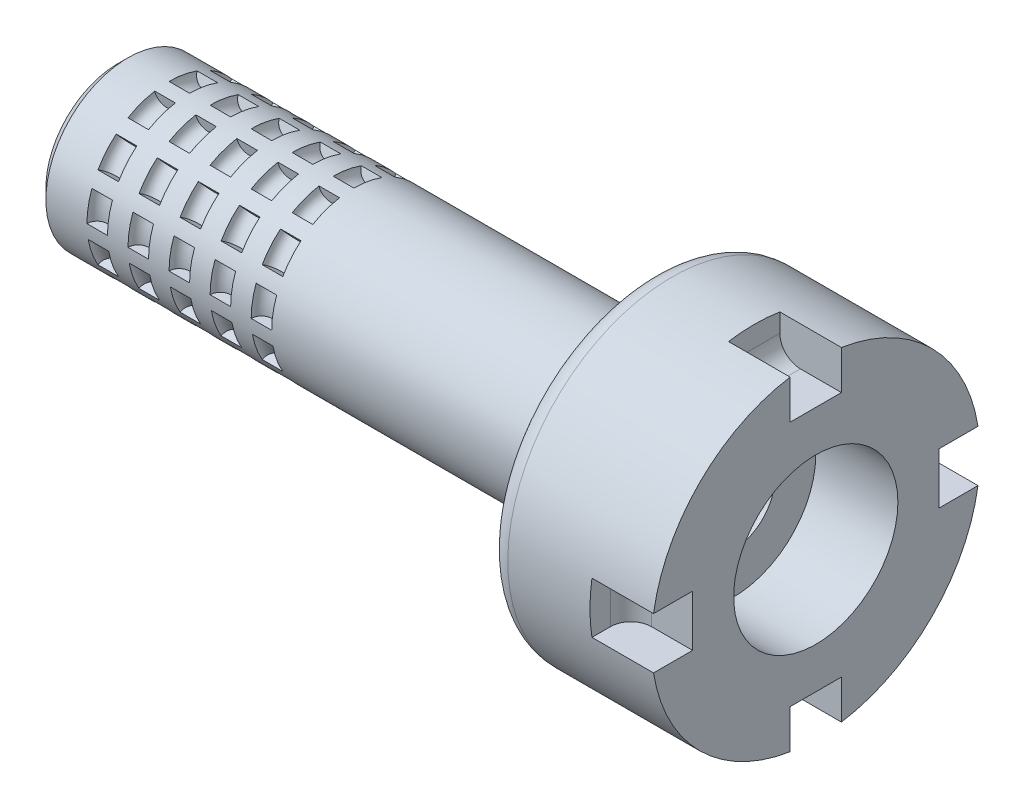
SolidWorks part; units mm, degrees
ref_plane "Płaszczyzna przednia" through (0, 0, 0) normal (0, 0, 1) x (1, 0, 0)
ref_plane "Płaszczyzna górna" through (0, 0, 0) normal (0, 1, 0) x (1, 0, 0)
ref_plane "Płaszczyzna prawa" through (0, 0, 0) normal (1, 0, 0) x (0, 0, -1)
sketch "Szkic1" plane through (0, 0, 0) normal (0, 0, 1) x (1, 0, 0)
  line L0 (0, 0) -> (340, 0) construction
  line L7 (0, 20) -> (340, 20)
  line L8 (340, 20) -> (340, 80)
  line L9 (340, 80) -> (260, 80)
  line L10 (260, 80) -> (260, 40)
  line L11 (0, 20) -> (0, 40)
  line L12 (0, 40) -> (260, 40)
  point P2 (260, 59.6893)
  point P3 (340, 0)
  point P10 (0, 0)
  point P11 (333.9782, 20)
  point P13 (326.9391, -28.2987)
  dimension "D1" = 80
  dimension "D2" = 340
  dimension "D3" = 40
  dimension "D4" = 160
  dimension "D5" = 80
revolve "Obrót1" add sketch "Szkic1" angle 360 about L0
sketch "Szkic3" plane through (340, 0, 0) normal (1, 0, 0) x (0, 0, -1)
  circle A0 centre (0, 0) radius 40
  dimension "D1" = 80
extrude "Wytnij-wyciągnięcie1" cut sketch "Szkic3" against normal blind 40
sketch "Szkic4" plane through (340, 0, 0) normal (1, 0, 0) x (0, 0, -1)
  line L1 (-12.5, 90) -> (12.5, 90)
  line L2 (-12.5, 90) -> (-12.5, 60)
  line L3 (-12.5, 60) -> (12.5, 60)
  line L4 (12.5, 90) -> (12.5, 60)
  dimension "D1" = 25
  dimension "D2" = 30
  dimension "D3" = 60
  dimension "D4" = 12.5
extrude "Wytnij-wyciągnięcie2" cut sketch "Szkic4" against normal blind 30
fillet "Zaokrąglenie1" radius 10 1 edges at (310, 60, 0)
pattern_circular "Szyk kołowy2" count 4 over 360 about axis through (0, 0, 0) along (-1, 0, 0) of "Zaokrąglenie1", "Wytnij-wyciągnięcie2"
fillet "Zaokrąglenie2" radius 10 2 edges at (260, 0, 40) (260, 0, 80)
chamfer "Sfazowanie1" distance 5 angle 45 1 edges at (0, 0, 40)
sketch "Szkic6" plane through (0, 0, 0) normal (0, 0, 1) x (1, 0, 0)
  line L0 (300, 0) -> (0, 0) construction
  line L1 (-7, 30) -> (8, 30)
  line L2 (-7, 30) -> (-7, 25)
  line L3 (-7, 25) -> (8, 25)
  line L4 (8, 30) -> (8, 25)
  point P4 (0, 0)
  point P5 (-10.4331, 18.7077)
  dimension "D1" = 5
  dimension "D2" = 15
  dimension "D3" = 25
  dimension "D4" = 8
revolve "Wycięcie-obrót1" cut sketch "Szkic6" angle 360 about axis through (0, 0, 0) along (-1, 0, 0)
fillet "Zaokrąglenie3" radius 2.5 3 edges at (8, 0, -30) (0, 0, -25) (8, 0, -25)
sketch "Szkic7" plane through (0, 0, 0) normal (0, 0, 1) x (1, 0, 0)
  line L0 (250, 40) -> (5, 40) construction
  circle A0 centre (30, 40) radius 5
  dimension "D1" = 10
  dimension "D2" = 30
revolve "Wycięcie-obrót3" cut sketch "Szkic7" angle 20 about axis through (0, 0, 0) along (-1, 0, 0)
pattern_circular "Szyk kołowy3" count 12 over 360 about axis through (0, 0, 0) along (-1, 0, 0) of "Wycięcie-obrót3"
pattern_linear "Szyk liniowy1" count 5 spacing 20 along (1, 0, 0) of "Szyk kołowy3"
